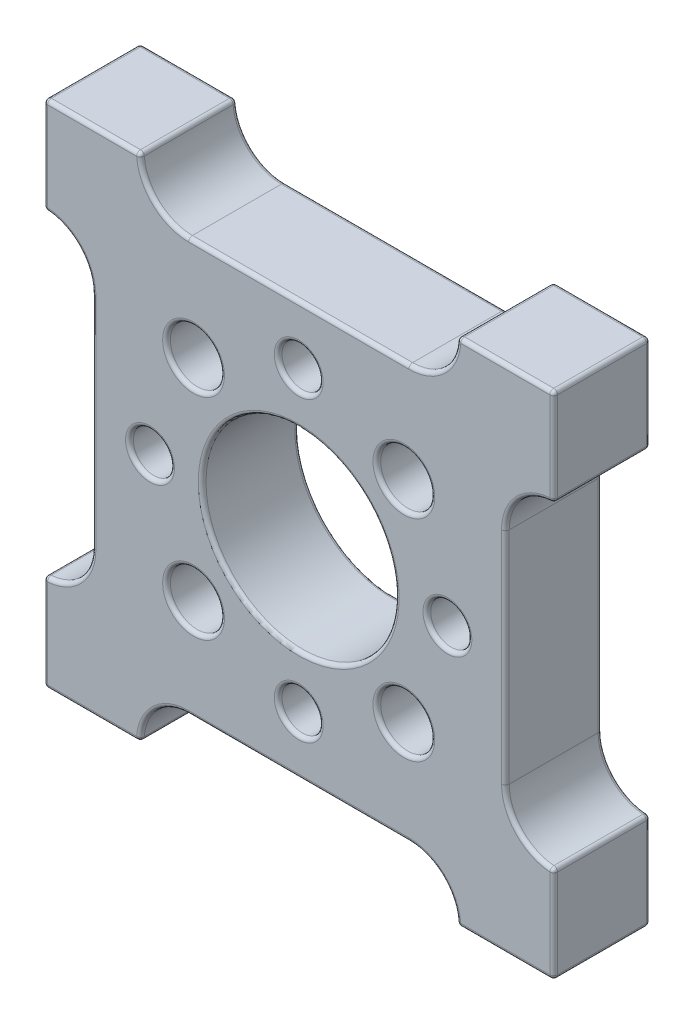
SolidWorks part; units mm, degrees
ref_plane "Front Plane" through (0, 0, 0) normal (0, 0, 1) x (1, 0, 0)
ref_plane "Top Plane" through (0, 0, 0) normal (0, 1, 0) x (1, 0, 0)
ref_plane "Right Plane" through (0, 0, 0) normal (1, 0, 0) x (0, 0, -1)
sketch "Sketch1" plane through (0, 0, 0) normal (0, 0, 1) x (1, 0, 0)
  line L0 (0, 0) -> (33.528, 33.528) construction
  line L1 (0, 0) -> (6.35, 0)
  line L2 (0, 0) -> (0, 6.35)
  line L3 (0, 33.528) -> (6.35, 33.528)
  line L4 (33.528, 0) -> (33.528, 6.35)
  line L5 (6.35, 30.353) -> (27.178, 30.353)
  line L6 (30.353, 6.35) -> (30.353, 27.178)
  line L7 (6.35, 3.175) -> (27.178, 3.175)
  line L8 (3.175, 6.35) -> (3.175, 27.178)
  line L9 (6.35, 0) -> (6.35, 3.175)
  line L10 (0, 27.178) -> (3.175, 27.178)
  line L11 (27.178, 0) -> (27.178, 3.175)
  line L12 (0, 6.35) -> (3.175, 6.35)
  line L13 (3.175, 30.353) -> (30.353, 30.353) construction
  line L14 (3.175, 3.175) -> (3.175, 30.353) construction
  line L15 (30.353, 3.175) -> (30.353, 30.353) construction
  line L16 (3.175, 3.175) -> (30.353, 3.175) construction
  line L17 (27.178, 33.528) -> (33.528, 33.528)
  line L18 (0, 27.178) -> (33.528, 27.178) construction
  line L19 (0, 33.528) -> (33.528, 33.528) construction
  line L20 (0, 6.35) -> (33.528, 6.35) construction
  line L21 (6.35, 30.353) -> (6.35, 33.528)
  line L22 (6.35, 0) -> (6.35, 33.528) construction
  line L23 (27.178, 30.353) -> (27.178, 33.528)
  line L24 (27.178, 0) -> (27.178, 33.528) construction
  line L25 (30.353, 6.35) -> (33.528, 6.35)
  line L26 (0, 27.178) -> (0, 33.528)
  line L27 (0, 0) -> (0, 33.528) construction
  line L28 (30.353, 27.178) -> (33.528, 27.178)
  line L29 (33.528, 27.178) -> (33.528, 33.528)
  line L30 (33.528, 0) -> (33.528, 33.528) construction
  line L31 (27.178, 0) -> (33.528, 0)
  line L32 (0, 0) -> (33.528, 0) construction
  circle A0 centre (16.764, 16.764) radius 6.35
  dimension "D3" = 12.7
  dimension "D1" = 33.528
  dimension "D2" = 33.528
  dimension "D4" = 3.175
  dimension "D5" = 6.35
  dimension "D6" = 6.35
  dimension "D7" = 6.35
  dimension "D8" = 6.35
extrude "Extrude1" add sketch "Sketch1" along normal blind 6.35
fillet "Fillet1" radius 3.175 8 edges at (27.178, 3.175, 3.175) (30.353, 6.35, 3.175) (6.35, 3.175, 3.175) (30.353, 27.178, 3.175) (3.175, 6.35, 3.175) (27.178, 30.353, 3.175) (6.35, 30.353, 3.175) (3.175, 27.178, 3.175)
sketch "Sketch2" plane through (0, 0, 6.35) normal (0, 0, 1) x (1, 0, 0)
  circle A0 centre (16.764, 16.764) radius 9.779 construction
  circle A1 centre (9.8492, 23.6788) radius 1.778
  circle A2 centre (9.8492, 9.8492) radius 1.778
  circle A3 centre (23.6788, 9.8492) radius 1.778
  circle A4 centre (23.6788, 23.6788) radius 1.778
  dimension "D1" = 19.558
  dimension "D2" = 3.556
extrude "Extrude2" cut sketch "Sketch2" against normal up to next
hole_wizard "#6-32 Tapped Hole1" positions "3DSketch1" profile "Sketch3" tap size "#6-32" standard "Ansi Inch" end condition up to next
sketch3d "3DSketch1"
  line L0 (16.764, 16.764, 6.35) -> (16.764, 16.764, 0) construction
  line L1 (16.764, 6.985, 6.35) -> (16.764, 26.543, 6.35) construction
  line L2 (6.985, 16.764, 6.35) -> (26.543, 16.764, 6.35) construction
  circle A0 centre (16.764, 16.764, 6.35) radius 9.779 construction
  point P3 (16.764, 16.764, 16.129)
  point P7 (16.764, 26.543, 6.35)
  point P9 (6.985, 16.764, 6.35)
  point P11 (16.764, 6.985, 6.35)
  point P13 (26.543, 16.764, 6.35)
sketch "Sketch3" plane through (16.764, 26.543, 6.35) normal (1, 0, 0) x (0, -1, 0)
  line L0 (0, 0) -> (0, 6.35)
  line L1 (0, 6.35) -> (1.3525, 6.35)
  line L2 (1.3525, 6.35) -> (1.3525, 0)
  line L5 (1.3525, 0) -> (0, 0)
  line L11 (0, -6.35) -> (0, 107.95) construction
  dimension "Thread Major Dia." = 2.7051
  dimension "Thru Tap Drill Depth" = 6.35
fillet "Fillet2" radius 0.254 70 edges at (0, 6.35, 3.175) (0, 0, 3.175) (6.35, 0, 3.175) (27.178, 0, 3.175) (33.528, 0, 3.175) (33.528, 6.35, 3.175) (33.528, 27.178, 3.175) (33.528, 33.528, 3.175) (27.178, 33.528, 3.175) (6.35, 33.528, 3.175) (0, 33.528, 3.175) (0, 27.178, 3.175) (23.114, 16.764, 0) (3.175, 0, 0) (7.2799, 2.2451, 0) (16.764, 3.175, 0) (26.2481, 2.2451, 0) (30.353, 0, 0) (33.528, 3.175, 0) (31.2829, 7.2799, 0) (30.353, 16.764, 0) (31.2829, 26.2481, 0) (33.528, 30.353, 0) (30.353, 33.528, 0) (26.2481, 31.2829, 0) (16.764, 30.353, 0) (7.2799, 31.2829, 0) (3.175, 33.528, 0) (0, 30.353, 0) (2.2451, 26.2481, 0) (3.175, 16.764, 0) (2.2451, 7.2799, 0) (0, 3.175, 0) (8.0712, 23.6788, 0) (8.0712, 9.8492, 0) (21.9008, 9.8492, 0) (21.9008, 23.6788, 0) (25.1905, 16.764, 0) (15.4115, 6.985, 0) (5.6324, 16.764, 0) (15.4115, 26.543, 0) (18.1165, 26.543, 6.35) (18.1165, 6.985, 6.35) (23.114, 16.764, 6.35) (2.2451, 7.2799, 6.35) (3.175, 16.764, 6.35) (2.2451, 26.2481, 6.35) (0, 30.353, 6.35) (3.175, 33.528, 6.35) (7.2799, 31.2829, 6.35) (16.764, 30.353, 6.35) (26.2481, 31.2829, 6.35) (30.353, 33.528, 6.35) (33.528, 30.353, 6.35) (31.2829, 26.2481, 6.35) (30.353, 16.764, 6.35) (31.2829, 7.2799, 6.35) (33.528, 3.175, 6.35) (30.353, 0, 6.35) (26.2481, 2.2451, 6.35) (16.764, 3.175, 6.35) (7.2799, 2.2451, 6.35) (3.175, 0, 6.35) (0, 3.175, 6.35) (11.6272, 23.6788, 6.35) (11.6272, 9.8492, 6.35) (25.4568, 9.8492, 6.35) (25.4568, 23.6788, 6.35) (27.8956, 16.764, 6.35) (8.3375, 16.764, 6.35)
